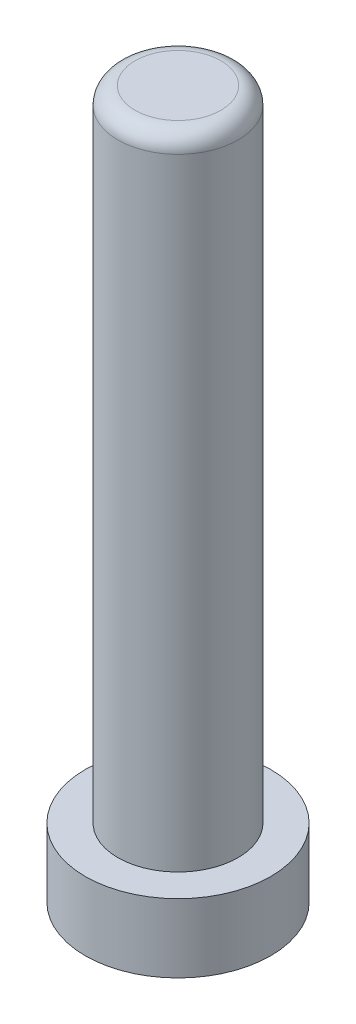
SolidWorks part; units mm, degrees
ref_plane "Front Plane" through (0, 0, 0) normal (0, 0, 1) x (1, 0, 0)
ref_plane "Top Plane" through (0, 0, 0) normal (0, 1, 0) x (1, 0, 0)
ref_plane "Right Plane" through (0, 0, 0) normal (1, 0, 0) x (0, 0, -1)
sketch "Sketch1" plane through (0, 0, 0) normal (0, 1, 0) x (1, 0, 0)
  line L1 (-2.8, -2.7) -> (2.8, -2.7) construction
  line L2 (-2.8, -2.7) -> (-2.8, 2.7) construction
  line L3 (-2.8, 2.7) -> (2.8, 2.7) construction
  line L4 (2.8, -2.7) -> (2.8, 2.7) construction
  line L5 (-2.8, -2.7) -> (2.8, 2.7) construction
  line L6 (-2.8, 2.7) -> (2.8, -2.7) construction
  circle A0 centre (0, 0) radius 2.7
  point P0 (0, 0)
  dimension "D1" = 5.6
  dimension "D2" = 5.4
extrude "Boss-Extrude1" add sketch "Sketch1" along normal blind 2
sketch "Sketch2" plane through (0, 2, 0) normal (0, 1, 0) x (1, 0, 0)
  circle A0 centre (0, 0) radius 1.75
  dimension "D1" = 3.5
sketch "Sketch3" plane through (0, 0, 0) normal (0, -1, 0) x (1, 0, 0)
  circle A0 centre (0, 0) radius 1.2
  circle A1 centre (0, 0) radius 0.95
  point P0 (0, 0)
  dimension "D1" = 2.4
  dimension "D2" = 1.9
extrude "Cut-Extrude2" cut sketch "Sketch3" against normal blind 9.5 contours A1
extrude "Boss-Extrude2" add sketch "Sketch2" along normal blind 18.6
sketch "Sketch7" plane through (0, 0, 0) normal (0, -1, 0) x (1, 0, 0)
  circle A0 centre (0, 0) radius 1.2
  dimension "D1" = 2.4
extrude "Cut-Extrude4" cut sketch "Sketch7" against normal blind 2.8
fillet "Fillet2" radius 0.5 1 edges at (0, 20.6, 1.75)
sketch "Sketch8" plane through (0, 0, 0) normal (0, -1, 0) x (1, 0, 0)
  circle A0 centre (0, 0) radius 0.95
  dimension "D1" = 1.9
extrude "Cut-Extrude5" cut sketch "Sketch8" against normal blind 9.5
